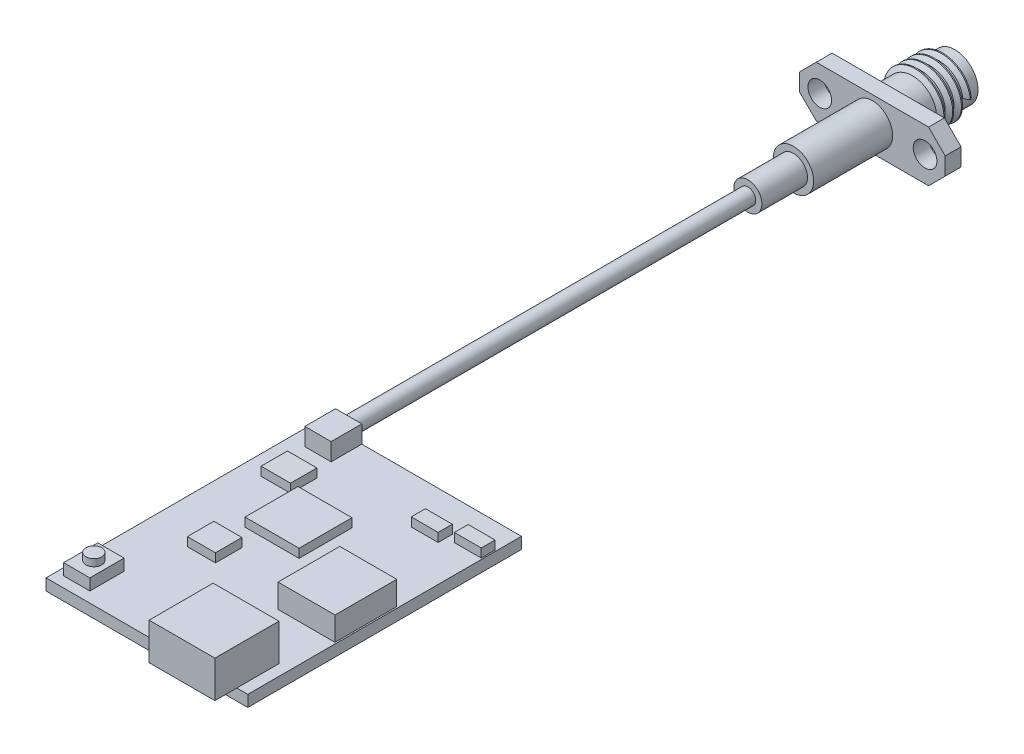
SolidWorks part; units mm, degrees
ref_plane "Front Plane" through (0, 0, 0) normal (0, 0, 1) x (1, 0, 0)
ref_plane "Top Plane" through (0, 0, 0) normal (0, 1, 0) x (1, 0, 0)
ref_plane "Right Plane" through (0, 0, 0) normal (1, 0, 0) x (0, 0, -1)
sketch "Sketch1" plane through (0, 0, 0) normal (0, 1, 0) x (1, 0, 0)
  line L1 (-11.5, -15.6) -> (11.5, -15.6)
  line L2 (-11.5, -15.6) -> (-11.5, 15.6)
  line L3 (-11.5, 15.6) -> (11.5, 15.6)
  line L4 (11.5, -15.6) -> (11.5, 15.6)
  line L5 (-11.5, -15.6) -> (11.5, 15.6) construction
  line L6 (-11.5, 15.6) -> (11.5, -15.6) construction
  point P0 (0, 0)
  dimension "D1" = 31.2
  dimension "D2" = 23
extrude "PCB" add sketch "Sketch1" along normal blind 1.3
sketch "Sketch2" plane through (0, 1.3, 0) normal (0, 1, 0) x (1, 0, 0)
  line L0 (-11.5, -15.6) -> (11.5, -15.6) construction
  line L1 (10.25, -10.8) -> (2.75, -10.8)
  line L2 (10.25, -10.8) -> (10.25, -18.1)
  line L3 (10.25, -18.1) -> (2.75, -18.1)
  line L4 (2.75, -10.8) -> (2.75, -18.1)
  line L5 (11.5, -15.6) -> (11.5, 15.6) construction
  dimension "D1" = 7.3
  dimension "D2" = 2.5
  dimension "D3" = 7.5
  dimension "D4" = 1.25
extrude "IO connector" add sketch "Sketch2" along normal blind 4.2
sketch "Sketch3" plane through (0, 1.3, 0) normal (0, 1, 0) x (1, 0, 0)
  line L0 (11.5, 15.6) -> (-11.5, 15.6) construction
  line L1 (-9.7, 15.6) -> (-6.7, 15.6)
  line L2 (-9.7, 15.6) -> (-9.7, 12.1)
  line L3 (-9.7, 12.1) -> (-6.7, 12.1)
  line L4 (-6.7, 15.6) -> (-6.7, 12.1)
  line L5 (-11.5, 15.6) -> (-11.5, -15.6) construction
  dimension "D1" = 3
  dimension "D2" = 3.5
  dimension "D3" = 1.8
extrude "Antenna connector" add sketch "Sketch3" along normal blind 2
sketch "Sketch4" plane through (0, 0, -15.6) normal (0, 0, -1) x (-1, 0, 0)
  line L0 (6.7, 2.3) -> (9.7, 2.3) construction
  line L1 (6.7, 3.3) -> (6.7, 1.3) construction
  line L2 (9.7, 3.3) -> (9.7, 1.3) construction
  line L3 (8.2, 3.3) -> (8.2, 0) construction
  line L4 (6.7, 3.3) -> (9.7, 3.3) construction
  line L5 (-11.5, 0) -> (11.5, 0) construction
  circle A0 centre (8.2, 2.3) radius 0.9
  dimension "D1" = 1.8
extrude "Antenna wire" add sketch "Sketch4" along normal blind 45.5
sketch "Sketch5" plane through (0, 0, -61.1) normal (0, 0, -1) x (-1, 0, 0)
  circle A0 centre (8.2, 2.3) radius 1.6
  dimension "D1" = 3.2
extrude "Antenna connector wire start" add sketch "Sketch5" along normal blind 5.2
sketch "Sketch6" plane through (0, 0, -66.3) normal (0, 0, -1) x (-1, 0, 0)
  circle A0 centre (8.2, 2.3) radius 2.3
  dimension "D1" = 4.6
extrude "Antenna connector wire end" add sketch "Sketch6" along normal blind 9
sketch "Sketch7" plane through (0, 0, -75.3) normal (0, 0, -1) x (-1, 0, 0)
  line L0 (-0.1, 2.3) -> (16.5, 2.3) construction
  line L1 (16.5, -0.6) -> (-0.1, -0.6)
  line L2 (16.5, -0.6) -> (16.5, 5.2)
  line L3 (16.5, 5.2) -> (-0.1, 5.2)
  line L4 (-0.1, -0.6) -> (-0.1, 5.2)
  line L5 (16.5, -0.6) -> (-0.1, 5.2) construction
  line L6 (16.5, 5.2) -> (-0.1, -0.6) construction
  line L7 (8.2, 5.2) -> (8.2, -0.6) construction
  line L8 (-0.1, 3.3) -> (1.8, 5.2)
  line L9 (16.5, 3.3) -> (14.6, 5.2)
  line L10 (16.5, 1.3) -> (14.6, -0.6)
  line L11 (-0.1, 1.3) -> (1.8, -0.6)
  circle A0 centre (2.2, 2.3) radius 1.35
  circle A1 centre (14.2, 2.3) radius 1.35
  point P0 (8.2, 2.3)
  circle M8 centre (8.2, 2.3) radius 2.3
  dimension "D3" = 2.7
  dimension "D1" = 5.8
  dimension "D2" = 16.6
  dimension "D4" = 12
  dimension "D5" = 45
  dimension "D6" = 2
extrude "Antenna connector mount" add sketch "Sketch7" along normal blind 1.8 contours L4 L11 L1 L10 L2 L9 L3 L8 A0 A1 M8 | M8 region at (-8.2, -0.4242, -75.3) region at (-8.2, 2.3, -75.3)
sketch "Sketch8" plane through (0, 0, -77.1) normal (0, 0, -1) x (-1, 0, 0)
  line L0 (-0.1, 2.3) -> (16.5, 2.3) construction
  line L1 (-0.1, 1.3) -> (-0.1, 3.3) construction
  line L2 (16.5, 1.3) -> (16.5, 3.3) construction
  line L3 (8.2, 5.2) -> (8.2, -0.6) construction
  line L4 (14.6, 5.2) -> (1.8, 5.2) construction
  line L5 (14.6, -0.6) -> (1.8, -0.6) construction
  circle A0 centre (8.2, 2.3) radius 2.64
  dimension "D1" = 5.28
extrude "Antenna connector shaft" add sketch "Sketch8" along normal blind 2.7
sketch "Sketch9" plane through (0, 0, -79.8) normal (0, 0, -1) x (-1, 0, 0)
  circle A0 centre (8.2, 2.3) radius 2.64
  circle A1 centre (8.2, 2.3) radius 2.64 construction
extrude "Antenna connector middle" add sketch "Sketch9" along normal blind 3.9
sketch "Sketch10" plane through (0, 0, -83.7) normal (0, 0, -1) x (-1, 0, 0)
  circle A0 centre (8.2, 2.3) radius 2.64
  circle A1 centre (8.2, 2.3) radius 2.64 construction
extrude "Antenna connector tip" add sketch "Sketch10" along normal blind 1
sketch "Sketch11" plane through (0, 0, -84.7) normal (0, 0, -1) x (-1, 0, 0)
  circle A0 centre (8.2, 2.3) radius 2.35
  dimension "D1" = 4.7
extrude "Antenna connector hole" cut sketch "Sketch11" against normal blind 1.9
sketch "Sketch12" plane through (0, 0, -82.8) normal (0, 0, -1) x (-1, 0, 0)
  circle A0 centre (8.2, 2.3) radius 0.5
  dimension "D1" = 1
extrude "Antenna connector mate" cut sketch "Sketch12" against normal blind 2.5
thread "Antenna connector thread" pitch 1 method extrude profile "Thread Profile1" start angle 0, offset 1, length 4, pitch 1, diameter 5.28
ref_plane "Plane1" through (-5.56, 2.3, -83.7) normal (0, -1, 0) x (1, 0, 0)
sketch "Thread Profile1" plane through (-5.56, 2.3, -83.7) normal (0, -1, 0) x (1, 0, 0)
  line L0 (0, 0) -> (0, 1) construction
  line L1 (0, 0) -> (0.5413, 0.3125)
  line L2 (0.5413, 0.3125) -> (0.5413, 0.4375)
  line L3 (0.5413, 0.4375) -> (0, 0.75)
  line L4 (0.5413, 0.375) -> (0, 0.375) construction
  line L11 (0, 0) -> (0, 0.75)
  point P2 (0, 0)
  dimension "Pitch" = 1
  dimension "Profile_Angle" = 60
  dimension "Profile_Land" = 0.125
  dimension "Profile_Height" = 0.5413
sketch "Sketch15" plane through (0, 1.3, 0) normal (0, 1, 0) x (1, 0, 0)
  line L0 (-11.5, 15.6) -> (-11.5, -15.6) construction
  line L1 (-10.7, -14.4) -> (-7.7, -14.4)
  line L2 (-10.7, -14.4) -> (-10.7, -10.5)
  line L3 (-10.7, -10.5) -> (-7.7, -10.5)
  line L4 (-7.7, -14.4) -> (-7.7, -10.5)
  line L5 (-11.5, -15.6) -> (2.75, -15.6) construction
  dimension "D1" = 3.9
  dimension "D2" = 3
  dimension "D3" = 0.8
  dimension "D4" = 1.2
extrude "Button base" add sketch "Sketch15" along normal blind 1.3
sketch "Sketch16" plane through (0, 2.6, 0) normal (0, 1, 0) x (1, 0, 0)
  line L0 (-10.7, -12.45) -> (-7.7, -12.45) construction
  line L1 (-10.7, -10.5) -> (-10.7, -14.4) construction
  line L2 (-7.7, -14.4) -> (-7.7, -10.5) construction
  line L3 (-9.2, -10.5) -> (-9.2, -14.4) construction
  line L4 (-7.7, -10.5) -> (-10.7, -10.5) construction
  line L5 (-10.7, -14.4) -> (-7.7, -14.4) construction
  circle A0 centre (-9.2, -12.45) radius 0.9
  dimension "D1" = 1.8
extrude "Button tip" add sketch "Sketch16" along normal blind 0.8
sketch "Sketch17" plane through (0, 1.3, 0) normal (0, 1, 0) x (1, 0, 0)
  line L1 (-5.1573, 6.7739) -> (1.0006, 6.7739)
  line L2 (-5.1573, 6.7739) -> (-5.1573, 0.7442)
  line L3 (-5.1573, 0.7442) -> (1.0006, 0.7442)
  line L4 (1.0006, 6.7739) -> (1.0006, 0.7442)
  line L5 (-5.9087, 6.6822) -> (-9.2626, 6.6822)
  line L6 (-5.9087, 6.6822) -> (-5.9087, 9.6879)
  line L7 (-5.9087, 9.6879) -> (-9.2626, 9.6879)
  line L8 (-9.2626, 6.6822) -> (-9.2626, 9.6879)
  line L9 (11.3555, 12.7302) -> (8.2948, 12.7302)
  line L10 (11.3555, 12.7302) -> (11.3555, 11.1541)
  line L11 (11.3555, 11.1541) -> (8.2948, 11.1541)
  line L12 (8.2948, 12.7302) -> (8.2948, 11.1541)
  line L13 (7.3601, 11.8505) -> (4.2995, 11.8505)
  line L14 (7.3601, 11.8505) -> (7.3601, 10.2377)
  line L15 (7.3601, 10.2377) -> (4.2995, 10.2377)
  line L16 (4.2995, 11.8505) -> (4.2995, 10.2377)
  line L17 (-3.3164, -1.4486) -> (-6.5178, -1.4486)
  line L18 (-3.3164, -1.4486) -> (-3.3164, -4.4695)
  line L19 (-3.3164, -4.4695) -> (-6.5178, -4.4695)
  line L20 (-6.5178, -1.4486) -> (-6.5178, -4.4695)
  point P20 (11.3555, 11.1541)
  point P21 (8.2948, 12.7302)
  point P22 (0, 0)
  point P23 (7.3601, 10.2377)
  point P24 (4.2995, 11.8505)
  point P25 (1.0006, 6.7739)
  point P26 (-5.1573, 0.7442)
  point P27 (-5.9087, 6.7739)
  point P28 (-9.171, 10.3843)
  point P29 (-3.3164, -4.4695)
  point P30 (-6.5178, -1.4486)
extrude "Low chips" add sketch "Sketch17" along normal blind 1
sketch "Sketch18" plane through (0, 1.3, 0) normal (0, 1, 0) x (1, 0, 0)
  line L1 (11.3334, -5.4928) -> (4.8405, -5.4928)
  line L2 (11.3334, -5.4928) -> (11.3334, 1.5455)
  line L3 (11.3334, 1.5455) -> (4.8405, 1.5455)
  line L4 (4.8405, -5.4928) -> (4.8405, 1.5455)
  point P4 (4.8405, -5.4928)
  point P5 (0, 0)
  point P6 (11.3334, 1.5455)
extrude "High chips" add sketch "Sketch18" along normal blind 2.7
